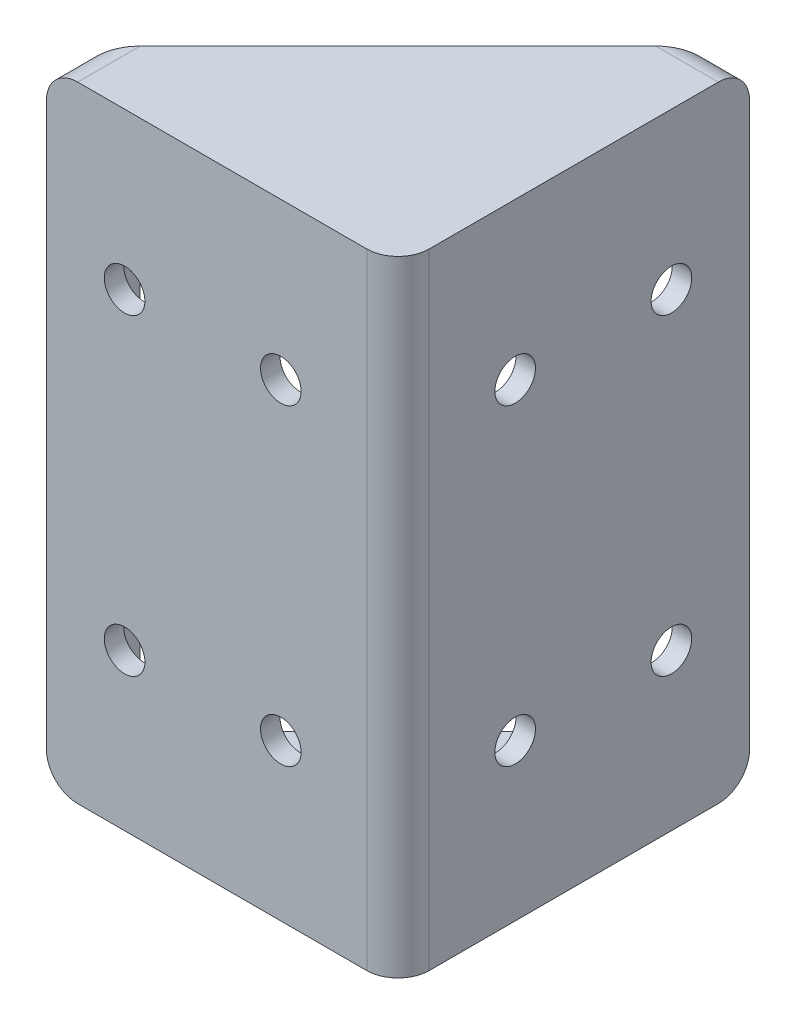
SolidWorks part; units mm, degrees
ref_plane "Front Plane" through (0, 0, 0) normal (0, 0, 1) x (1, 0, 0)
ref_plane "Top Plane" through (0, 0, 0) normal (0, 1, 0) x (1, 0, 0)
ref_plane "Right Plane" through (0, 0, 0) normal (1, 0, 0) x (0, 0, -1)
sketch "Sketch1" plane through (0, 0, 0) normal (0, 0, 1) x (1, 0, 0)
  line L0 (-19.225, -34.0959) -> (25.775, -34.0959)
  line L1 (-19.225, -34.0959) -> (-19.225, 45.9041)
  line L2 (-19.225, 45.9041) -> (25.775, 45.9041)
  line L3 (25.775, -34.0959) -> (25.775, 45.9041)
  dimension "D1" = 45
  dimension "D2" = 80
extrude "Boss-Extrude1" add sketch "Sketch1" along normal blind 45
sketch "Sketch3" plane through (0, 0, 45) normal (0, 0, 1) x (-1, 0, 0)
  line L1 (-10.775, -25.9041) -> (9.225, -25.9041) construction
  line L2 (-10.775, -25.9041) -> (-10.775, 14.0959) construction
  line L3 (-10.775, 14.0959) -> (9.225, 14.0959) construction
  line L4 (9.225, -25.9041) -> (9.225, 14.0959) construction
  line L5 (-10.775, -25.9041) -> (9.225, 14.0959) construction
  line L6 (-10.775, 14.0959) -> (9.225, -25.9041) construction
  line L9 (-25.775, 34.0959) -> (-25.775, -45.9041) construction
  line L11 (19.225, -45.9041) -> (19.225, 34.0959) construction
  circle A0 centre (-10.775, -25.9041) radius 2.6
  circle A1 centre (-10.775, 14.0959) radius 2.6
  circle A2 centre (9.225, 14.0959) radius 2.6
  circle A3 centre (9.225, -25.9041) radius 2.6
  point P0 (-0.775, -5.9041)
  point P16 (-25.775, -5.9041)
  dimension "D3" = 5.2
  dimension "D1" = 40
  dimension "D2" = 20
  dimension "D4" = 10
extrude "Cut-Extrude1" cut sketch "Sketch3" against normal blind 40
shell "Shell1" thickness 4 removed face at (3.275, 5.9041, 0)
sketch "Sketch4" plane through (0, 45.9041, 0) normal (0, 1, 0) x (1, 0, 0)
  line L0 (-19.225, 0) -> (-19.225, -41)
  line L1 (-19.225, -45) -> (-19.225, 0) construction
  line L2 (-19.225, -41) -> (21.775, 0)
  line L3 (21.775, 0) -> (-19.225, 0)
  line L4 (25.775, -45) -> (-19.225, -45) construction
  dimension "D1" = 4
  dimension "D2" = 4
extrude "Cut-Extrude2" cut sketch "Sketch4" against normal through all
sketch "Sketch5" plane through (0, 0, 41) normal (0, 0, -1) x (-1, 0, 0)
  line L1 (-21.775, 41.9041) -> (15.225, 41.9041)
  line L2 (-21.775, 41.9041) -> (-21.775, -30.0959)
  line L3 (-21.775, -30.0959) -> (15.225, -30.0959)
  line L4 (15.225, 41.9041) -> (15.225, -30.0959)
extrude "Cut-Extrude3" cut sketch "Sketch5" along normal blind 40
sketch "Sketch6" plane through (25.775, 0, 0) normal (1, 0, 0) x (0, 0, 1)
  line L0 (45, 34.0959) -> (45, -45.9041) construction
  line L1 (10, -25.9041) -> (30, -25.9041) construction
  line L2 (10, -25.9041) -> (10, 14.0959) construction
  line L3 (10, 14.0959) -> (30, 14.0959) construction
  line L4 (30, -25.9041) -> (30, 14.0959) construction
  line L5 (10, -25.9041) -> (30, 14.0959) construction
  line L6 (10, 14.0959) -> (30, -25.9041) construction
  line L10 (0, 34.0959) -> (0, -45.9041) construction
  circle A0 centre (10, -25.9041) radius 2.6
  circle A1 centre (10, 14.0959) radius 2.6
  circle A2 centre (30, 14.0959) radius 2.6
  circle A3 centre (30, -25.9041) radius 2.6
  point P0 (20, -5.9041)
  point P11 (45, -5.9041)
  dimension "D3" = 5.2
  dimension "D1" = 40
  dimension "D2" = 20
  dimension "D4" = 10
extrude "Cut-Extrude4" cut sketch "Sketch6" against normal blind 40
fillet "Fillet1" radius 4 5 edges at (3.275, -30.0959, 41) (21.775, -30.0959, 20.5) (21.775, 41.9041, 20.5) (21.775, 5.9041, 41) (3.275, 41.9041, 41)
fillet "Fillet2" radius 4 4 edges at (-19.225, -34.0959, 43) (-19.225, 45.9041, 43) (23.775, 45.9041, 0) (23.775, -34.0959, 0)
fillet "Fillet3" radius 4 1 edges at (25.775, 5.9041, 45)
sketch "Sketch7" plane through (21.775, 0, 0) normal (-1, 0, 0) x (0, 0, 1)
  circle A0 centre (10, 25.9041) radius 6.25
  circle A1 centre (30, 25.9041) radius 6.25
  circle A2 centre (30, -14.0959) radius 6.25
  circle A3 centre (10, -14.0959) radius 6.25
  dimension "D1" = 12.5
sketch "Sketch8" plane through (0, 0, 41) normal (0, 0, -1) x (-1, 0, 0)
  circle A0 centre (-10.775, -14.0959) radius 6.25
  circle A1 centre (-10.775, 25.9041) radius 6.25
  circle A2 centre (9.225, 25.9041) radius 6.25
  circle A3 centre (9.225, -14.0959) radius 6.25
  dimension "D1" = 12.5
extrude "Cut-Extrude5" cut sketch "Sketch8" against normal blind 1.5
extrude "Cut-Extrude6" cut sketch "Sketch7" against normal blind 1.5
